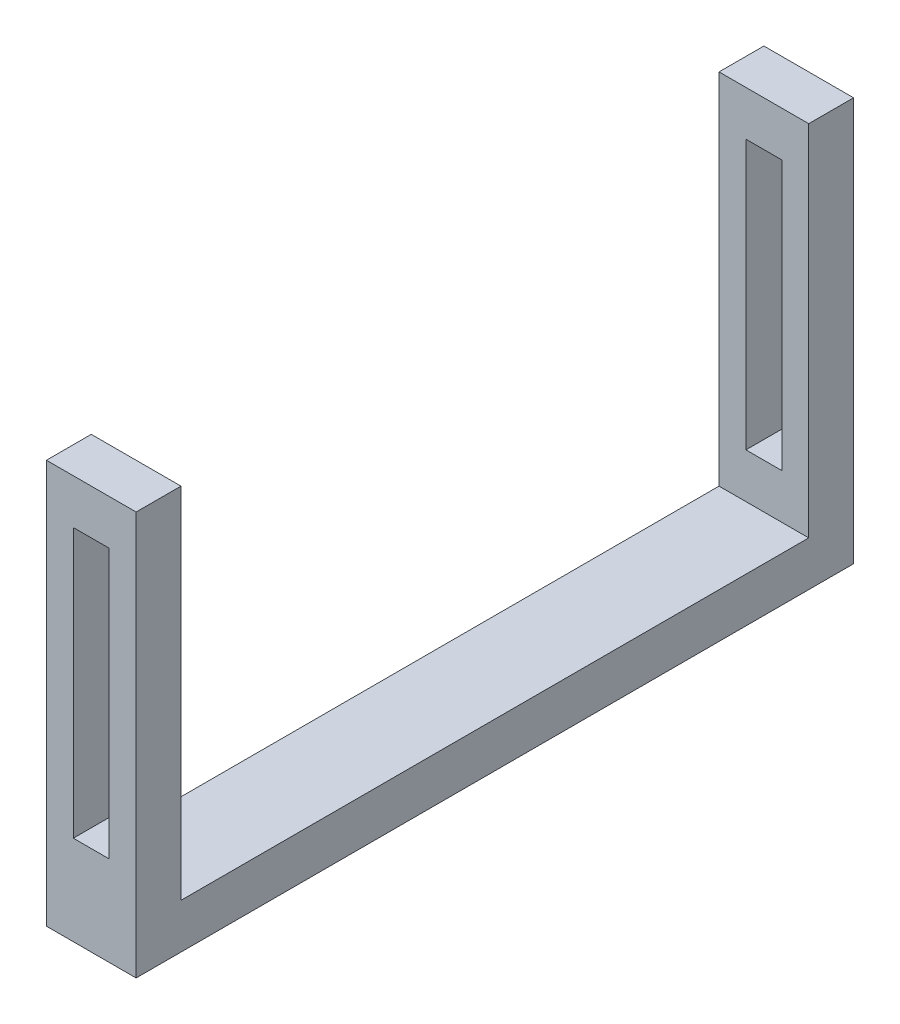
SolidWorks part; units mm, degrees
ref_plane "Plano frontal" through (0, 0, 0) normal (0, 0, 1) x (1, 0, 0)
ref_plane "Plano superior" through (0, 0, 0) normal (0, 1, 0) x (1, 0, 0)
ref_plane "Plano direito" through (0, 0, 0) normal (1, 0, 0) x (0, 0, -1)
sketch "Esboço1" plane through (0, 0, 0) normal (0, 0, 1) x (1, 0, 0)
  line L17 (-10, -40) -> (10, -40)
  line L18 (-10, -40) -> (-10, 40)
  line L19 (-10, 40) -> (10, 40)
  line L20 (10, -40) -> (10, 40)
  line L21 (-4, -30) -> (4, -30)
  line L22 (-4, -30) -> (-4, 30)
  line L23 (-4, 30) -> (4, 30)
  line L24 (4, -30) -> (4, 30)
  line L25 (-4, -30) -> (4, 30) construction
  line L26 (-4, 30) -> (4, -30) construction
  line L27 (-10, -40) -> (10, -40)
  line L28 (-10, -40) -> (-10, -50)
  line L29 (-10, -50) -> (10, -50)
  line L30 (10, -40) -> (10, -50)
  point P0 (0, 0)
extrude "Ressalto-extrusão1" add sketch "Esboço1" along normal blind 10 contours L17 L20 L19 L18 L24 L21 L22 L23 region at (-9.1754, 0, 0)
extrude "Ressalto-extrusão3" add sketch "Esboço1<4>" along normal blind 80 contours L30 L17 L28 L29 region at (0, -45, 0)
sketch "Esboço1<4>" plane through (0, 0, 0) normal (0, 0, 1) x (1, 0, 0) same geometry as "Esboço1"
ref_plane "Plano1" through (0, 0, 80) normal (0, 0, 1) x (1, 0, 0)
mirror "Espelhar2" about plane through (0, 0, 80) normal (0, 0, 1) of "Ressalto-extrusão1", "Ressalto-extrusão3"
